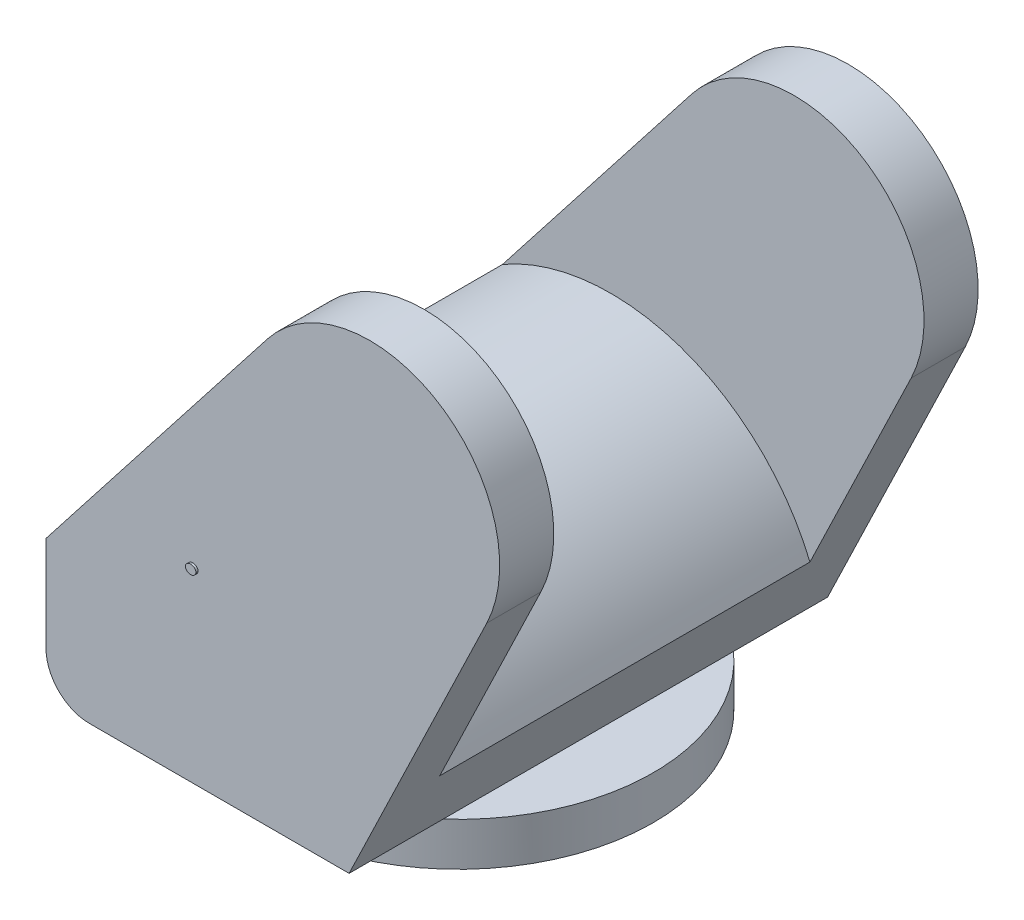
SolidWorks part; units mm, degrees
ref_plane "Front Plane" through (0, 0, 0) normal (0, 0, 1) x (1, 0, 0)
ref_plane "Top Plane" through (0, 0, 0) normal (0, 1, 0) x (1, 0, 0)
ref_plane "Right Plane" through (0, 0, 0) normal (1, 0, 0) x (0, 0, -1)
sketch "Sketch1" plane through (0, 0, 0) normal (1, 0, 0) x (0, 0, -1)
  line L0 (-64.2929, -51.1093) -> (55.7071, -51.1093)
  line L1 (75.7071, -31.1093) -> (75.7071, 12.8907)
  line L2 (75.7071, 12.8907) -> (-26.5576, 143.7893)
  line L3 (-64.2929, -51.1093) -> (-127.8857, 80.7938)
  arc A0 (-26.5576, 143.7893) -> (-127.8857, 80.7938) centre (-73.839, 106.8507) ccw
  arc A1 (75.7071, -31.1093) -> (55.7071, -51.1093) centre (55.7071, -31.1093) cw
  dimension "D1" = 20
  dimension "D3" = 120
  dimension "D2" = 120
  dimension "D4" = 44
  dimension "D5" = 157.96
  dimension "D6" = 166.11
extrude "Boss-Extrude1" add sketch "Sketch1" along normal blind 110.5 and the other way blind 110.5
sketch "Sketch2" plane through (0, 0, 0) normal (1, 0, 0) x (0, 0, -1)
  line L0 (-127.8857, 80.7938) -> (-64.2929, -51.1093) construction
  line L1 (75.7071, 12.8907) -> (-26.5576, 143.7893) construction
  line L2 (-127.8857, 80.7938) -> (-81.1498, -16.1449)
  line L3 (60.8576, 31.898) -> (-26.5576, 143.7893)
  arc A0 (-26.5576, 143.7893) -> (-127.8857, 80.7938) centre (-73.839, 106.8507) ccw construction
  arc A1 (-26.5576, 143.7893) -> (-127.8857, 80.7938) centre (-73.839, 106.8507) ccw
  arc A2 (60.8576, 31.898) -> (-81.1498, -16.1449) centre (10.8457, -54.1718) ccw
extrude "Cut-Extrude1" cut sketch "Sketch2" against normal blind 85.5 and the other way blind 85.5 contours A1 L2 A2 L3
sketch "Sketch3" plane through (0, -51.1093, 0) normal (0, -1, 0) x (1, 0, 0)
  line L0 (-110.5, 64.2929) -> (110.5, 64.2929) construction
  circle A0 centre (0, 4.2929) radius 90
  dimension "D1" = 180
  dimension "D2" = 60
extrude "Boss-Extrude2" add sketch "Sketch3" along normal blind 20 contours A0
move or copy body "Body-Move/Copy1" bodies to move or copy 103 copy no rotation origin (0, 0, 0) rotation axis (0, 1, 0) rotation angle 90
sketch "Sketch4" plane through (0, 0, 110.5) normal (0, 0, 1) x (1, 0, 0)
  text T0 "." font "Century Gothic" height 25
extrude "Boss-Extrude3" add sketch "Sketch4" along normal blind 1
sketch "Sketch5" plane through (0, 0, 0) normal (0, 0, 1) x (1, 0, 0)
  point P0 (73.839, 106.8507)
move or copy body "Body-Move/Copy2" bodies to move or copy 105 copy no translate (-73.839, -106.8507, 0)
